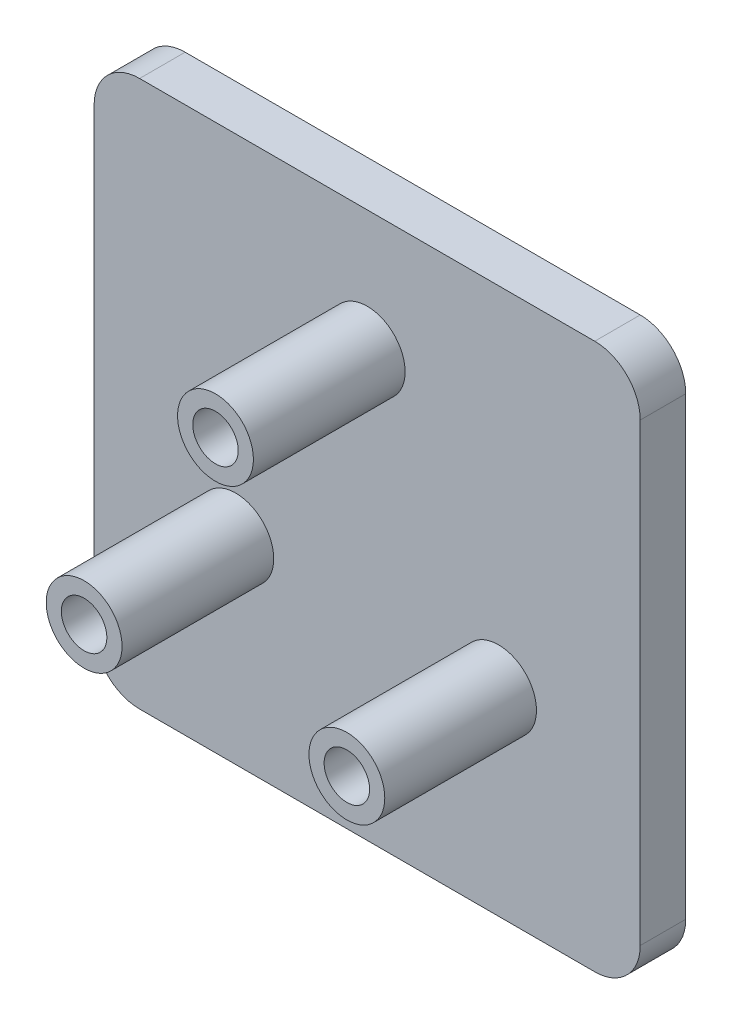
SolidWorks part; units mm, degrees
ref_plane "Front Plane" through (0, 0, 0) normal (0, 0, 1) x (1, 0, 0)
ref_plane "Top Plane" through (0, 0, 0) normal (0, 1, 0) x (1, 0, 0)
ref_plane "Right Plane" through (0, 0, 0) normal (1, 0, 0) x (0, 0, -1)
sketch "Sketch1" plane through (0, 0, 0) normal (0, 0, 1) x (1, 0, 0)
  line L0 (0, 18) -> (0, -18) construction
  line L1 (-15, -18) -> (15, -18)
  line L2 (-18, -15) -> (-18, 15)
  line L3 (-15, 18) -> (15, 18)
  line L4 (18, -15) -> (18, 15)
  line L5 (-18, -18) -> (18, 18) construction
  line L6 (-18, 18) -> (18, -18) construction
  arc A0 (-15, -18) -> (-18, -15) centre (-15, -15) cw
  arc A1 (15, -18) -> (18, -15) centre (15, -15) ccw
  arc A2 (15, 18) -> (18, 15) centre (15, 15) cw
  arc A3 (-18, 15) -> (-15, 18) centre (-15, 15) cw
  circle A4 centre (0, 10) radius 2.5
  circle A5 centre (0, 10) radius 1.5
  circle A6 centre (8.6603, -5) radius 1.5
  circle A7 centre (8.6603, -5) radius 2.5
  circle A8 centre (-8.6603, -5) radius 1.5
  circle A9 centre (-8.6603, -5) radius 2.5
  point P0 (0, 0)
  dimension "D3" = 3
  dimension "D5" = 5
  dimension "D6" = 3
  dimension "D1" = 36
  dimension "D2" = 36
  dimension "D4" = 10
  dimension "D7" = 3
extrude "Boss-Extrude1" add sketch "Sketch1" along normal blind 3 contours A3 L2 A0 L1 A1 L4 A2 L3 A9 A7 A4 | A8 | A9 A8 | A4 A5 | A5 | A7 A6 | A6 region at (0, 0, 0) region at (-2.4293, 10, 0) region at (0, 10, 0) region at (8.6603, -5, 0) region at (6.231, -5, 0) region at (-8.6603, -5, 0) region at (-11.0895, -5, 0)
extrude "Boss-Extrude2" add sketch "Sketch1<3>" along normal blind 10 from surface contours A9 A8 | A4 A5 | A7 A6 region at (-2.4293, 10, 0) region at (6.231, -5, 0) region at (-11.0895, -5, 0) starting at face at (0, 0, 3)
sketch "Sketch1<3>" plane through (0, 0, 0) normal (0, 0, 1) x (1, 0, 0) same geometry as "Sketch1"
